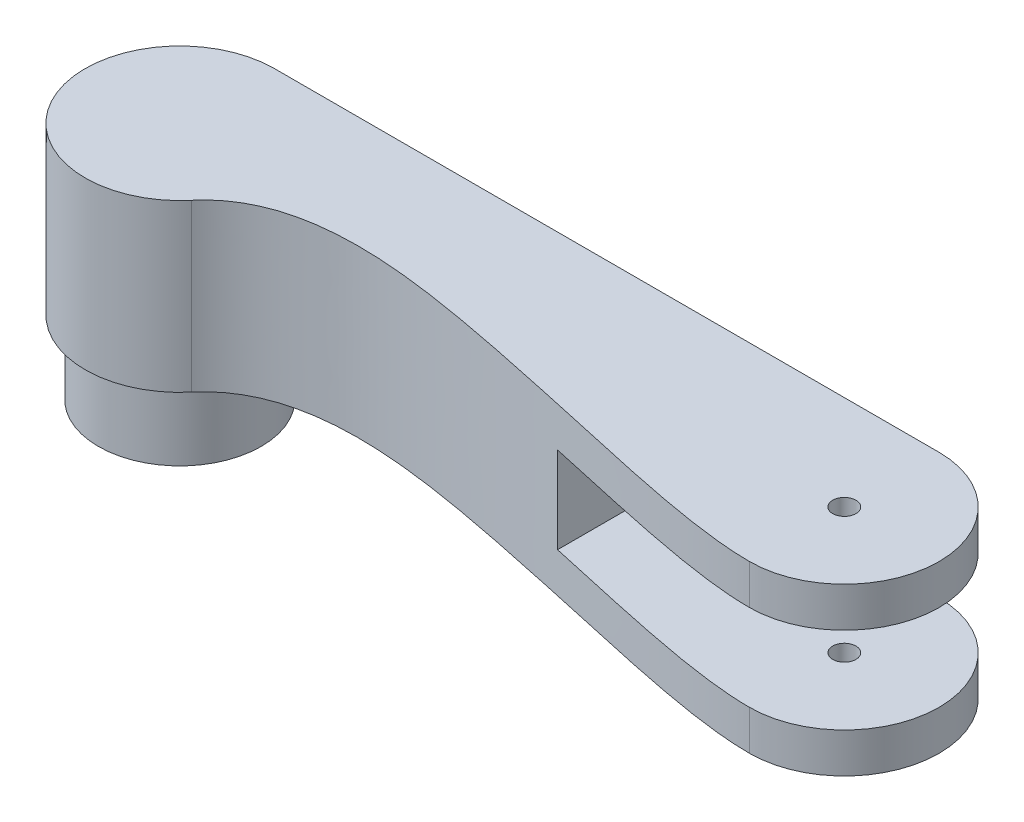
SolidWorks part; units mm, degrees
ref_plane "Front Plane" through (0, 0, 0) normal (0, 0, 1) x (1, 0, 0)
ref_plane "Top Plane" through (0, 0, 0) normal (0, 1, 0) x (1, 0, 0)
ref_plane "Right Plane" through (0, 0, 0) normal (1, 0, 0) x (0, 0, -1)
sketch "Sketch1" plane through (0, 0, 0) normal (0, 1, 0) x (1, 0, 0)
  line L0 (-50, 0) -> (50, 0) construction
  line L1 (-50, 14.25) -> (50, 14.25)
  line L2 (-50, -14.25) -> (50, -14.25)
  arc A0 (-50, 14.25) -> (-50, -14.25) centre (-50, 0) ccw
  arc A1 (50, -14.25) -> (50, 14.25) centre (50, 0) ccw
  point P3 (0, 0)
  dimension "D1" = 14.25
  dimension "D2" = 100
extrude "Boss-Extrude1" add sketch "Sketch1" along normal blind 6
sketch "Sketch3" plane through (0, 0, 0) normal (0, -1, 0) x (1, 0, 0)
  circle A0 centre (50, 0) radius 1.75
  dimension "D1" = 3.5
extrude "Cut-Extrude2" cut sketch "Sketch3" against normal through all
sketch "Sketch4" plane through (0, 6, 0) normal (0, 1, 0) x (1, 0, 0)
  line L0 (-50, 14.25) -> (15, 14.25)
  line L1 (-50, 14.25) -> (50, 14.25) construction
  line L2 (15, 14.25) -> (15, -14.25)
  line L3 (-50, -14.25) -> (50, -14.25) construction
  line L4 (15, -14.25) -> (-50, -14.25)
  arc A0 (-50, 14.25) -> (-50, -14.25) centre (-50, 0) ccw
  arc A1 (-50, 14.25) -> (-50, -14.25) centre (-50, 0) ccw construction
  dimension "D1" = 65
extrude "Boss-Extrude2" add sketch "Sketch4" along normal blind 13
sketch "Sketch5" plane through (0, 19, 0) normal (0, 1, 0) x (1, 0, 0)
  line L0 (-50, 0) -> (50, 0) construction
  line L1 (-50, 14.25) -> (50, 14.25)
  line L2 (-50, -14.25) -> (50, -14.25)
  arc A0 (-50, 14.25) -> (-50, -14.25) centre (-50, 0) ccw
  arc A1 (50, -14.25) -> (50, 14.25) centre (50, 0) ccw
  point P4 (0, 0)
  dimension "D1" = 14.25
extrude "Boss-Extrude3" add sketch "Sketch5" along normal blind 6
sketch "Sketch6" plane through (0, 25, 0) normal (0, 1, 0) x (1, 0, 0)
  circle A0 centre (50, 0) radius 1.75
  dimension "D1" = 3.5
extrude "Cut-Extrude3" cut sketch "Sketch6" against normal up to next
sketch "Sketch7" plane through (0, 25, 0) normal (0, 1, 0) x (1, 0, 0)
  line L0 (0, -15.6753) -> (0, 15.6753) construction
  line L1 (-50, -14.25) -> (50, -14.25)
  circle A0 centre (-50, 0) radius 14.25
  circle A1 centre (50, 0) radius 14.25
  spline S0 degree 3 poles (-39.0732, -9.1469) (-31.5141, -0.117) (5.4387, -4.6452) (38.6975, -14.25) (50, -14.25) knots 0 0 0 0 0.435908 1 1 1 1
  line M5 (-50, -14.25) -> (50, -14.25)
extrude "Cut-Extrude4" cut sketch "Sketch7" against normal up to next contours S0 A0 M5 region at (-8.5907, 25, 9.7914)
sketch "Sketch8" plane through (0, 0, 0) normal (0, -1, 0) x (1, 0, 0)
  circle A1 centre (-50, 0) radius 12.25
  dimension "D1" = 24.5
extrude "Boss-Extrude4" add sketch "Sketch8" along normal blind 11
sketch "Sketch9" plane through (0, -11, 0) normal (0, -1, 0) x (1, 0, 0)
  circle A0 centre (-50, 0) radius 6.75 construction
  circle A1 centre (-50, 6.75) radius 2.55
  circle A2 centre (-50, -6.75) radius 2.55
  arc A3 (-50, 14.25) -> (-50, -14.25) centre (-50, 0) ccw construction
  circle A4 centre (-50, 0) radius 3
  point P6 (-50, 0)
  dimension "D1" = 13.5
  dimension "D2" = 5.1
  dimension "D3" = 6
extrude "Cut-Extrude5" cut sketch "Sketch9" against normal blind 6
equation "\"Length\"= 100mm"
equation "\"Radius\"= 14.25mm"
equation "\"Thick\"= 12mm"
equation "\"D1@Sketch1\"= \"Radius\""
equation "\"D2@Sketch1\" = \"Length\""
equation "\"D1@Boss-Extrude1\"= \"Thick\""
equation "\"D1@Sketch4\"=\"Length\"*0.65"
equation "\"D1@Sketch5\"=\"Radius\""
equation "\"D1@Boss-Extrude4\"=\"Thick\"-1"
